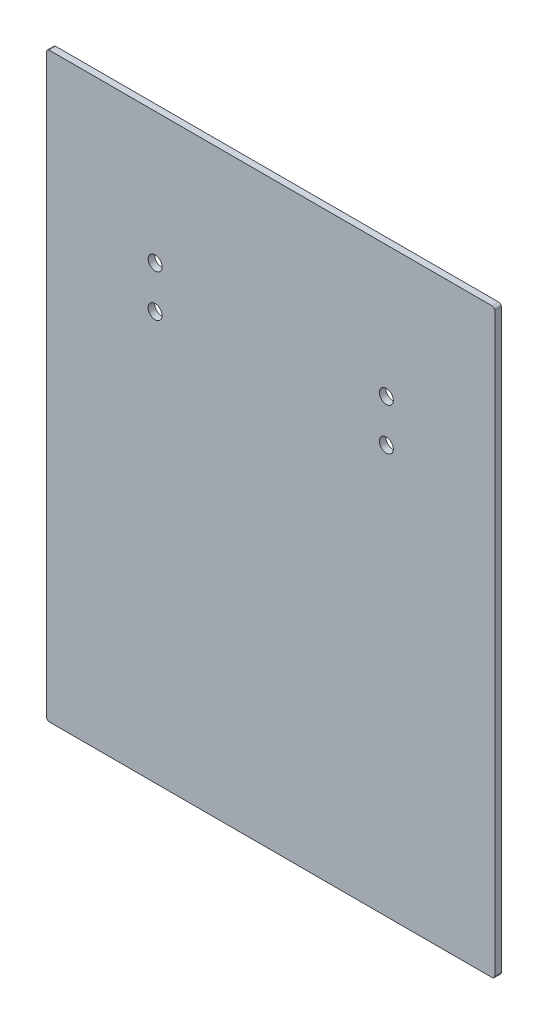
SolidWorks part; units mm, degrees
material "Plain Carbon Steel"
ref_plane "Front Plane" through (0, 0, 0) normal (0, 0, 1) x (1, 0, 0)
ref_plane "Top Plane" through (0, 0, 0) normal (0, 1, 0) x (1, 0, 0)
ref_plane "Right Plane" through (0, 0, 0) normal (1, 0, 0) x (0, 0, -1)
sketch "Sketch1" plane through (0, 0, 0) normal (0, 0, 1) x (1, 0, 0)
  line L0 (355.6, -484.2272) -> (0, 0) construction
  line L1 (0, 0) -> (0, 38.1) construction
  line L2 (393.7, -522.3669) -> (-38.1, -522.3669)
  line L3 (393.7, -522.3669) -> (393.7, 38.1)
  line L4 (393.7, 38.1) -> (-38.1, 38.1)
  line L5 (-38.1, -522.3669) -> (-38.1, 38.1)
  line L6 (393.7, -522.3669) -> (-38.1, 38.1) construction
  line L7 (393.7, 38.1) -> (-38.1, -522.3669) construction
  line L8 (-25.4, -21.4312) -> (-25.4, 21.4312) construction
  line L9 (0, 0) -> (-38.1, 0) construction
  point P4 (177.8, -242.1334)
  dimension "D1" = 12.7
extrude "Boss-Extrude1" add sketch "Sketch1" along normal blind 6.35
fillet "Fillet1" radius 2.54 4 edges at (393.7, 38.1, 3.175) (393.7, -522.3669, 3.175) (-38.1, -522.3669, 3.175) (-38.1, 38.1, 3.175)
sketch "Sketch3" plane through (0, 0, 0) normal (0, 0, -1) x (-1, 0, 0)
  line L0 (-177.8, 38.1) -> (-177.8, -522.3669) construction
  line L1 (-391.16, 38.1) -> (35.56, 38.1) construction
  line L2 (35.56, -522.3669) -> (-391.16, -522.3669) construction
  line L3 (-177.8, -108.745) -> (-289.1714, -108.745) construction
  line L4 (-289.1714, -88.425) -> (-289.1714, -129.065) construction
  point P8 (-289.1714, -88.425)
  point P9 (-289.1714, -129.065)
  point P12 (0, 0)
  point P13 (-66.4286, -129.065)
  point P14 (-66.4286, -88.425)
  dimension "D1" = 40.64
  dimension "D2" = 126.525
  dimension "D3" = 222.7428
hole_wizard "1/2 Clearance Hole1" positions "Sketch3" profile "Sketch4" hole size "1/2" standard "ANSI Inch" end condition up to next
sketch "Sketch4" plane through (66.4286, -88.425, 0) normal (1, 0, 0) x (0, 1, 0)
  line L0 (0, 0) -> (0, 6.35)
  line L1 (0, 6.35) -> (6.7462, 6.35)
  line L2 (6.7462, 6.35) -> (6.7462, 0)
  line L5 (6.7462, 0) -> (0, 0)
  line L11 (0, -6.35) -> (0, 107.95) construction
  dimension "Thru Hole Dia." = 13.4925
  dimension "Thru Hole Depth" = 6.35
